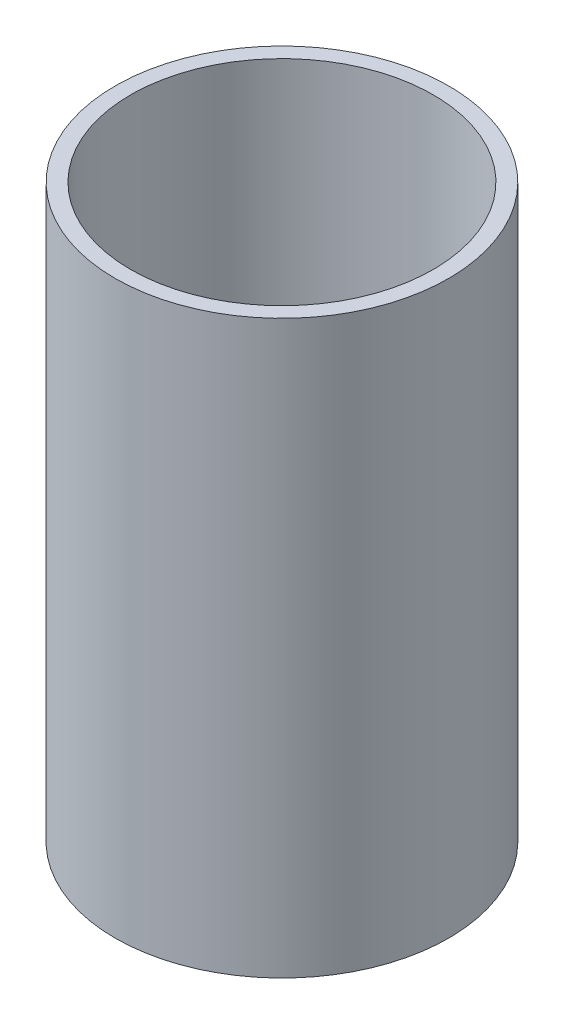
SolidWorks part; units mm, degrees
ref_plane "Front Plane" through (0, 0, 0) normal (0, 0, 1) x (1, 0, 0)
ref_plane "Top Plane" through (0, 0, 0) normal (0, 1, 0) x (1, 0, 0)
ref_plane "Right Plane" through (0, 0, 0) normal (1, 0, 0) x (0, 0, -1)
sketch "Sketch1" plane through (0, 0, 0) normal (0, 1, 0) x (1, 0, 0)
  line L0 (-5.35, 1.25) -> (-5.35, 0.5)
  line L1 (7.35, 0.5) -> (2.35, 0.5)
  line L2 (-2.35, 0.5) -> (-2.35, -1.25)
  line L3 (-2.35, -1.25) -> (2.35, -1.25)
  line L4 (-2.35, 1.25) -> (-2.35, 0.5)
  line L5 (-2.35, 1.25) -> (-2.35, 3.85)
  line L6 (2.35, 1.25) -> (2.35, 3.85)
  line L7 (5.35, 1.25) -> (5.35, 0.5)
  line L8 (-5.35, 3.85) -> (-5.35, 4.6)
  line L9 (-6.6, 3.85) -> (6.6, 3.85)
  line L10 (-2.35, 1.25) -> (-6.6, 1.25)
  line L11 (-7.35, 0.5) -> (-2.35, 0.5)
  line L12 (2.35, 1.25) -> (2.35, 0.5)
  line L13 (2.35, -1.25) -> (2.35, 0.5)
  line L14 (5.35, 3.85) -> (5.35, 4.6)
  line L15 (2.35, 1.25) -> (6.6, 1.25)
  line L17 (-6.6, 3.85) -> (-6.6, 1.25)
  line L18 (-7.35, 4.6) -> (7.35, 4.6)
  line L19 (6.6, 3.85) -> (6.6, 1.25)
  line L20 (-7.35, 4.6) -> (-7.35, 0.5)
  line L21 (-2.35, 1.25) -> (2.35, -1.25) construction
  line L22 (7.35, 4.6) -> (7.35, 0.5)
  line L23 (2.35, 1.25) -> (-2.35, -1.25) construction
  circle A15 centre (0, 0) radius 10.8
  circle A16 centre (0, 0) radius 9.8
  point P15 (0, 0)
  dimension "D2" = 0.75
  dimension "D3" = 0.75
  dimension "D4" = 0.75
  dimension "D5" = 2
  dimension "D6" = 2
  dimension "D7" = 3
  dimension "D8" = 3
  dimension "D9" = 2.6
  dimension "D10" = 4.7
  dimension "D11" = 2.5
extrude "Boss-Extrude7" add sketch "Sketch1" along normal blind 37 contours A15 A16 region at (-10.4945, 0, 0)
extrude "Boss-Extrude8" add sketch "Sketch1<10>" along normal blind 1 contours A16 L18 L22 L15 L19 L9 L17 L10 L11 L20 region at (-9.5228, 0, 0)
sketch "Sketch1<10>" plane through (0, 0, 0) normal (0, 1, 0) x (1, 0, 0) same geometry as "Sketch1"
extrude "Boss-Extrude9" add sketch "Sketch1<12>" along normal blind 5 contours L22 L18 L20 L11 L17 L9 L19 | L18 L8 L9 L14 | L22 L18 L14 L9 L19 L15 L7 L1 region at (-5.3956, 0, -0.875) region at (0, 0, -4.225) region at (5.3956, 0, -4.225)
sketch "Sketch1<12>" plane through (0, 0, 0) normal (0, 1, 0) x (1, 0, 0) same geometry as "Sketch1"
extrude "Boss-Extrude10" add sketch "Sketch1<13>" along normal blind 2 contours L11 L10 | L15 region at (-3.85, 0, -0.875) region at (3.85, 0, -0.875)
sketch "Sketch1<13>" plane through (0, 0, 0) normal (0, 1, 0) x (1, 0, 0) same geometry as "Sketch1"
extrude "Boss-Extrude11" add sketch "Sketch1<14>" along normal blind 0.5 contours L9 L17 L10 L5 | L19 L9 L6 L15 region at (-4.475, 0, -2.55) region at (4.475, 0, -2.55)
sketch "Sketch1<14>" plane through (0, 0, 0) normal (0, 1, 0) x (1, 0, 0) same geometry as "Sketch1"
extrude "Boss-Extrude12" add sketch "Sketch1<15>" along normal blind 20 contours L18 L20 L11 L0 L10 L17 L9 L8 | L22 L18 L14 L9 L19 L15 L7 L1 region at (-5.3956, 0, -0.875) region at (5.3956, 0, -4.225)
sketch "Sketch1<15>" plane through (0, 0, 0) normal (0, 1, 0) x (1, 0, 0) same geometry as "Sketch1"
